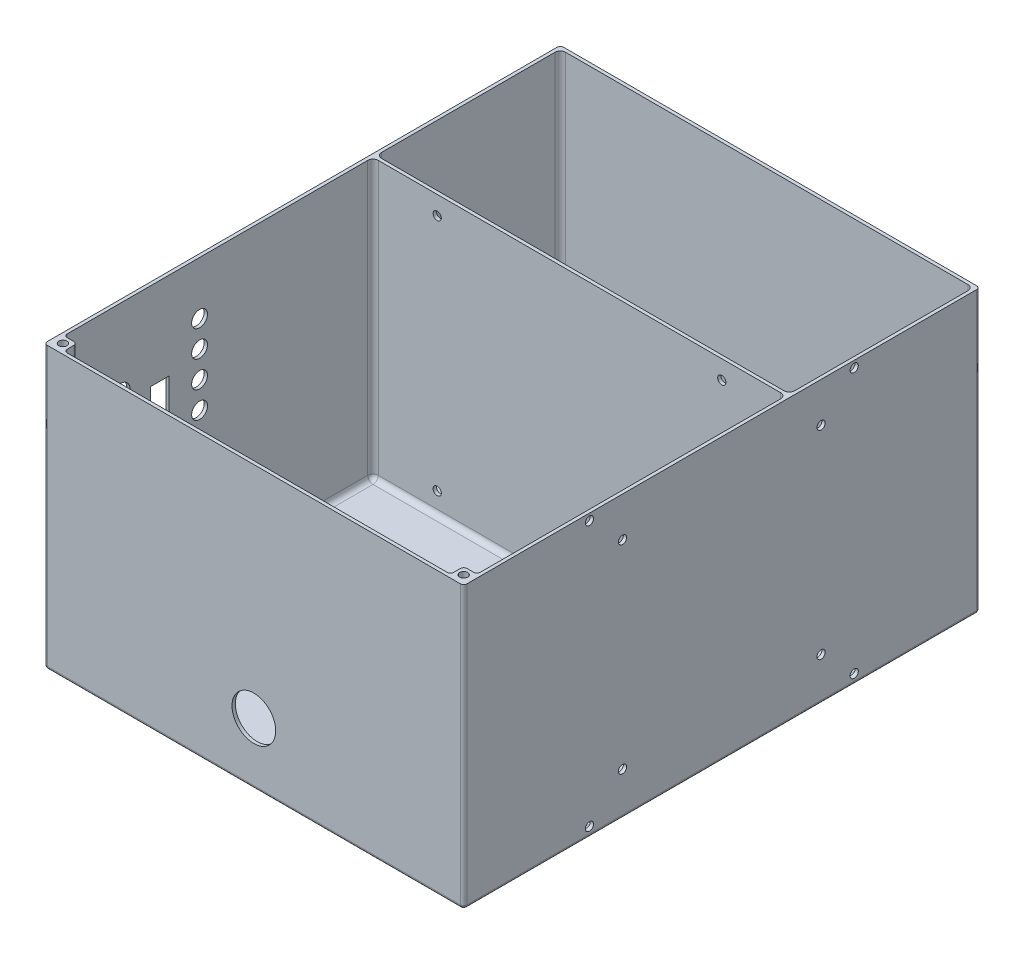
SolidWorks part; units mm, degrees
ref_plane "Front Plane" through (0, 0, 0) normal (0, 0, 1) x (1, 0, 0)
ref_plane "Top Plane" through (0, 0, 0) normal (0, 1, 0) x (1, 0, 0)
ref_plane "Right Plane" through (0, 0, 0) normal (1, 0, 0) x (0, 0, -1)
sketch "Sketch1" plane through (0, 0, 0) normal (0, 1, 0) x (1, 0, 0)
  line L0 (79.25, -36) -> (79.25, 36)
  line L1 (-78, -34.75) -> (78, -34.75)
  line L2 (-78, -34.75) -> (-78, 34.75)
  line L3 (-78, 34.75) -> (78, 34.75)
  line L4 (78, -34.75) -> (78, 34.75)
  line L5 (-78, -34.75) -> (78, 34.75) construction
  line L6 (-78, 34.75) -> (78, -34.75) construction
  line L7 (-79.25, 36) -> (79.25, 36)
  line L8 (-79.25, -36) -> (-79.25, 36)
  line L9 (-78, -36) -> (78, -36)
  line L10 (-78, -36) -> (-78, -86)
  line L11 (-78, -36) -> (78, -36)
  line L12 (-79.25, -36) -> (-79.25, -86)
  line L13 (-79.25, -86) -> (-79.25, -159)
  line L14 (79.25, -36) -> (79.25, -86)
  line L15 (78, -36) -> (78, -86)
  line L16 (-79.25, -36) -> (79.25, -36) construction
  line L17 (-78, -86) -> (-78, -100.5886)
  line L18 (79.25, -86) -> (79.25, -159)
  line L19 (78, -86) -> (78, -157.75)
  line L20 (79.25, -159) -> (-79.25, -159)
  line L21 (78, -159) -> (79.25, -159)
  line L22 (-78, -100.5886) -> (-78, -157.75)
  line L23 (-78, -157.75) -> (78, -157.75)
  line L24 (-78, -157.75) -> (78, -157.75) construction
  line L25 (0, -157.75) -> (0, -117.25)
  line L26 (-40, -117.25) -> (40, -117.25)
  line L27 (-34, -117.25) -> (34, -117.25)
  line L28 (-40, -117.25) -> (-34, -117.25) construction
  circle A0 centre (-37, -117.25) radius 3
  point P0 (0, 0)
  point P27 (0, -117.25)
  point P30 (0, -117.25)
  dimension "D1" = 156
  dimension "D2" = 69.5
  dimension "D4" = 50
  dimension "D5" = 195
  dimension "D6" = 1.25
  dimension "D7" = 40.5
  dimension "D8" = 80
  dimension "D9" = 68
  dimension "D3" = 1.25
sketch "Sketch2" plane through (0, 0, 0) normal (0, 1, 0) x (1, 0, 0)
  line L0 (-79.25, 36) -> (79.25, 36)
  line L1 (79.25, 36) -> (79.25, -159)
  line L2 (79.25, -159) -> (-79.25, -159)
  line L3 (-79.25, -159) -> (-79.25, 36)
extrude "Boss-Extrude1" add sketch "Sketch2" against normal blind 1.25
extrude "Boss-Extrude2" add sketch "Sketch1" along normal blind 105 contours L20 L18 L14 L0 L7 L8 L12 L13 L23 L22 L17 L10 L9 L15 L19 L4 L1 L2 L3 region at (78.9987, 0, 61)
sketch "Sketch4" plane through (0, 0, 0) normal (0, 1, 0) x (1, 0, 0)
  line L0 (-78, -157.75) -> (78, -157.75) construction
  line L1 (0, -157.75) -> (0, -117.75)
  line L2 (0, -5.0875) -> (0, 5.0875) construction
  line L3 (-34, -117.75) -> (34, -117.75)
  line L4 (-40.15, -117.75) -> (-39.575, -117.75)
  line L5 (-40.15, -117.75) -> (-39.575, -117.75) construction
  line L6 (34, -117.75) -> (34.575, -117.75) construction
  line L7 (-34.575, -117.75) -> (34.575, -117.75)
  line L8 (-34.575, -117.75) -> (-34, -117.75) construction
  line L9 (39.575, -117.75) -> (40.15, -117.75) construction
  line L10 (39.575, -117.75) -> (40.15, -117.75)
  circle A0 centre (-37.075, -117.75) radius 2.5
  circle A1 centre (37.075, -117.75) radius 2.5
  point P12 (0, -117.75)
  point P15 (0, -117.75)
  dimension "D1" = 40
  dimension "D2" = 68
  dimension "D3" = 80.3
extrude "Boss-Extrude3" add sketch "Sketch4" along normal blind 8 contours A0 | A1 region at (37.075, 0, 117.75) region at (-37.075, 0, 117.75)
fillet "Fillet2" radius 2 18 edges at (-78, 0, 0) (0, 0, -34.75) (78, 0, 0) (0, 0, 34.75) (0, 0, 36) (78, 0, 96.875) (0, 0, 157.75) (-78, 0, 96.875) (-37.075, 0, 115.25) (37.075, 0, 115.25) (78, 52.5, -34.75) (-78, 52.5, -34.75) (78, 52.5, 34.75) (-78, 52.5, 34.75) (-78, 52.5, 157.75) (78, 52.5, 157.75) (78, 52.5, 36) (-78, 52.5, 36)
sketch "Sketch5" plane through (0, 0, 36) normal (0, 0, 1) x (1, 0, 0)
  line L0 (-76, 105) -> (76, 105) construction
  line L2 (-76, 105) -> (-76, 2) construction
  line L3 (-58.75, 4.5) -> (58.75, 4.5)
  line L4 (-58.75, 4.5) -> (-58.75, 101.5)
  line L5 (-58.75, 101.5) -> (58.75, 101.5)
  line L6 (58.75, 4.5) -> (58.75, 101.5)
  line L7 (-58.75, 53) -> (58.75, 53)
  line L8 (-53.75, 101.5) -> (-53.75, 98)
  line L14 (-58.75, 98) -> (-53.75, 98)
  line L15 (0, 53) -> (0, 77.907)
  circle A0 centre (-53.75, 98) radius 1.55
  circle A1 centre (-53.75, 8) radius 1.55
  circle A2 centre (53.75, 8) radius 1.55
  circle A3 centre (53.75, 98) radius 1.55
  point P8 (0, 53.5)
  point P29 (0, 0)
  dimension "D1" = 97
  dimension "D2" = 117.5
  dimension "D3" = 17.25
  dimension "D4" = 3.5
  dimension "D5" = 5
  dimension "D6" = 3.5
extrude "Cut-Extrude1" cut sketch "Sketch5" against normal blind 8 contours L14 A0 L8 | L8 A0 L14 | A3 | A1 | A2 region at (-54.4078, 98.6578, 36) region at (-53.5307, 97.7807, 36) region at (-53.75, 8, 36) region at (53.75, 98, 36)
sketch "Sketch6" plane through (0, 0, 157.75) normal (0, 0, -1) x (-1, 0, 0)
  line L0 (-76, 2) -> (76, 2) construction
  line L1 (0, 2) -> (0, 22)
  line L2 (0, 5.0875) -> (0, -5.0875) construction
  circle A0 centre (0, 22) radius 8.25
  dimension "D1" = 20
extrude "Cut-Extrude2" cut sketch "Sketch6" against normal blind 8 contours A0 region at (-5.6686, 16.3314, 157.75)
sketch "Sketch8" plane through (-79.25, 0, 0) normal (-1, 0, 0) x (0, 0, 1)
  line L0 (159, 55) -> (116.5, 55)
  line L1 (159, -1.25) -> (159, 105) construction
  line L2 (116.5, 5) -> (116.5, 105)
  line L3 (159, 105) -> (-36, 105) construction
  line L4 (116.5, 55) -> (101.5, 55)
  line L5 (116.5, 55) -> (131.5, 55)
  line L7 (113, 58) -> (120, 58)
  line L8 (113, 58) -> (113, 72)
  line L9 (113, 72) -> (120, 72)
  line L10 (120, 58) -> (120, 72)
  line L11 (113, 58) -> (120, 72) construction
  line L12 (113, 72) -> (120, 58) construction
  circle A0 centre (101.5, 55) radius 3
  circle A1 centre (101.5, 65) radius 3
  circle A2 centre (101.5, 75) radius 3
  circle A3 centre (101.5, 85) radius 3
  circle A4 centre (131.5, 55) radius 3.75
  circle A5 centre (131.5, 75) radius 3.75
  point P9 (116.5, 55)
  point P13 (116.5, 65)
  dimension "D4" = 4
  dimension "D5" = 2
  dimension "D1" = 42.5
  dimension "D2" = 15
  dimension "D3" = 15
  dimension "D6" = 7
  dimension "D7" = 14
  dimension "D8" = 10
  dimension "D9" = 50
extrude "Cut-Extrude3" cut sketch "Sketch8" against normal blind 8 contours A0 | A2 | A3 | A1 | A5 | L8 L9 L10 L7 | A4 region at (-79.25, 55, 98.5849) region at (-79.25, 65, 101.5) region at (-79.25, 75, 101.5) region at (-79.25, 85, 101.5) region at (-79.25, 75, 131.5)
fillet "Fillet3" radius 1.25 4 edges at (0, -1.25, 159) (79.25, -1.25, 61.5) (0, -1.25, -36) (-79.25, -1.25, 61.5)
fillet "Fillet4" radius 1.25 8 edges at (-78.8839, -0.8839, 158.6339) (78.8839, -0.8839, 158.6339) (78.8839, -0.8839, -35.6339) (-78.8839, -0.8839, -35.6339) (-79.25, 52.5, 159) (79.25, 52.5, 159) (79.25, 52.5, -36) (-79.25, 52.5, -36)
sketch "Sketch11" plane through (79.25, 0, 0) normal (1, 0, 0) x (0, 0, -1)
  line L0 (-157.75, 105) -> (34.75, 0) construction
  line L1 (34.75, 105) -> (-157.75, 0)
  line L2 (87.175, 0) -> (-87.175, 0) construction
  line L4 (-111.5, 102.5) -> (-11.5, 102.5)
  line L5 (-111.5, 102.5) -> (-111.5, 2.5)
  line L6 (-111.5, 2.5) -> (-11.5, 2.5)
  line L7 (-11.5, 102.5) -> (-11.5, 2.5)
  line L8 (-111.5, 102.5) -> (-11.5, 2.5) construction
  line L9 (-111.5, 2.5) -> (-11.5, 102.5) construction
  line L10 (-99, 15) -> (-24, 15)
  line L11 (-99, 15) -> (-99, 90)
  line L12 (-99, 90) -> (-24, 90)
  line L13 (-24, 15) -> (-24, 90)
  line L14 (-99, 15) -> (-24, 90) construction
  line L15 (-99, 90) -> (-24, 15) construction
  circle A0 centre (-11.5, 102.5) radius 1.55
  circle A1 centre (-111.5, 102.5) radius 1.55
  circle A2 centre (-99, 90) radius 1.55
  circle A3 centre (-24, 90) radius 1.55
  circle A4 centre (-99, 15) radius 1.55
  circle A5 centre (-111.5, 2.5) radius 1.55
  circle A6 centre (-11.5, 2.5) radius 1.55
  circle A7 centre (-24, 15) radius 1.55
  point P9 (-61.5, 52.5)
  point P14 (-61.5, 52.5)
  dimension "D1" = 100
  dimension "D2" = 100
  dimension "D3" = 75
  dimension "D4" = 75
extrude "Cut-Extrude4" cut sketch "Sketch11" against normal blind 8 contours L7 A0 L4 | L4 A0 L7 | L13 A3 L12 | L12 A3 L13 | L6 A6 L7 | L5 A5 L6 | L6 A5 L5 | L11 A4 L10 | L10 A4 L11 | L10 A7 L13 | L13 A7 L10 | A1 | A2 | A6 region at (79.25, 101.8422, 12.1578) region at (79.25, 102.7193, 11.2807) region at (79.25, 2.2807, 11.2807) region at (79.25, 14.7807, 23.7807) region at (79.25, 15.6578, 24.6578) region at (79.25, 89.3422, 24.6578) region at (79.25, 90.2193, 23.7807) region at (79.25, 15.6578, 98.3422) region at (79.25, 14.7807, 99.2193) region at (79.25, 2.2807, 111.7193) region at (79.25, 3.1578, 110.8422)
sketch "Sketch12" plane through (0, 105, 0) normal (0, 1, 0) x (1, 0, 0)
  line L0 (0, -155.75) -> (0, -144.3132)
  line L1 (-78, -157.75) -> (-73, -157.75)
  line L2 (-78, -157.75) -> (-78, -152.75)
  line L3 (-78, -152.75) -> (-73, -152.75)
  line L4 (-73, -157.75) -> (-73, -152.75)
  line L5 (-76, -155.75) -> (76, -155.75) construction
  line L6 (0, -5.0875) -> (0, 5.0875) construction
  line L7 (78, -152.75) -> (73, -152.75)
  line L8 (73, -157.75) -> (73, -152.75)
  line L9 (78, -157.75) -> (73, -157.75)
  line L10 (78, -157.75) -> (78, -152.75)
  line M6 (76, -157.75) -> (-76, -157.75)
  arc M7 (-76, -157.75) -> (-78, -155.75) centre (-76, -155.75) cw
  line M8 (-78, -155.75) -> (-78, -38)
  line M12 (78, -38) -> (78, -155.75)
  arc M13 (78, -155.75) -> (76, -157.75) centre (76, -155.75) cw
  dimension "D1" = 5
  dimension "D2" = 5
extrude "Boss-Extrude5" add sketch "Sketch12" against normal up to surface (105 mm away) contours L8 L7 M6 M13 M12 | L4 L3 M6 M8 M7 region at (75.427, 105, 155.177) region at (-75.427, 105, 155.177) up to face at (0, 0, 96.875)
fillet "Fillet5" radius 1.25 14 edges at (78, 53.5, 152.75) (77.4142, 0.5858, 152.75) (74.5, 0, 152.75) (73, 0, 154.25) (73, 0.5858, 157.1642) (-73, 0, 154.25) (-73, 0.5858, 157.1642) (-74.5, 0, 152.75) (-77.4142, 0.5858, 152.75) (73, 53.5, 157.75) (73, 52.5, 152.75) (-73, 53.5, 157.75) (-78, 53.5, 152.75) (-73, 52.5, 152.75)
sketch "Sketch14" plane through (0, 105, 0) normal (0, 1, 0) x (1, 0, 0)
  line L0 (78, -38) -> (78, -151.5) construction
  line L1 (73.3661, -153.1161) -> (78, -153.1161)
  line L2 (73.3661, -153.1161) -> (73.3661, -157.75)
  line L3 (73.3661, -157.75) -> (78, -157.75)
  line L4 (78, -153.1161) -> (78, -157.75)
  line L5 (73.3661, -153.1161) -> (78, -157.75) construction
  line L6 (78, -157.75) -> (78.0536, -157.7607) construction
  line L7 (0, -157.75) -> (0, -147.0716)
  line L8 (-71.75, -157.75) -> (71.75, -157.75) construction
  line L9 (0, -58.4375) -> (0, 58.4375) construction
  arc A0 (74.25, -152.75) -> (73, -154) centre (74.25, -154) ccw construction
  circle A1 centre (75.6831, -155.4331) radius 1.525
  circle A2 centre (-75.6831, -155.4331) radius 1.525
extrude "Cut-Extrude5" cut sketch "Sketch14" against normal blind 8 contours A1 | A2 region at (75.6831, 105, 155.4331) region at (-75.6831, 105, 155.4331)
